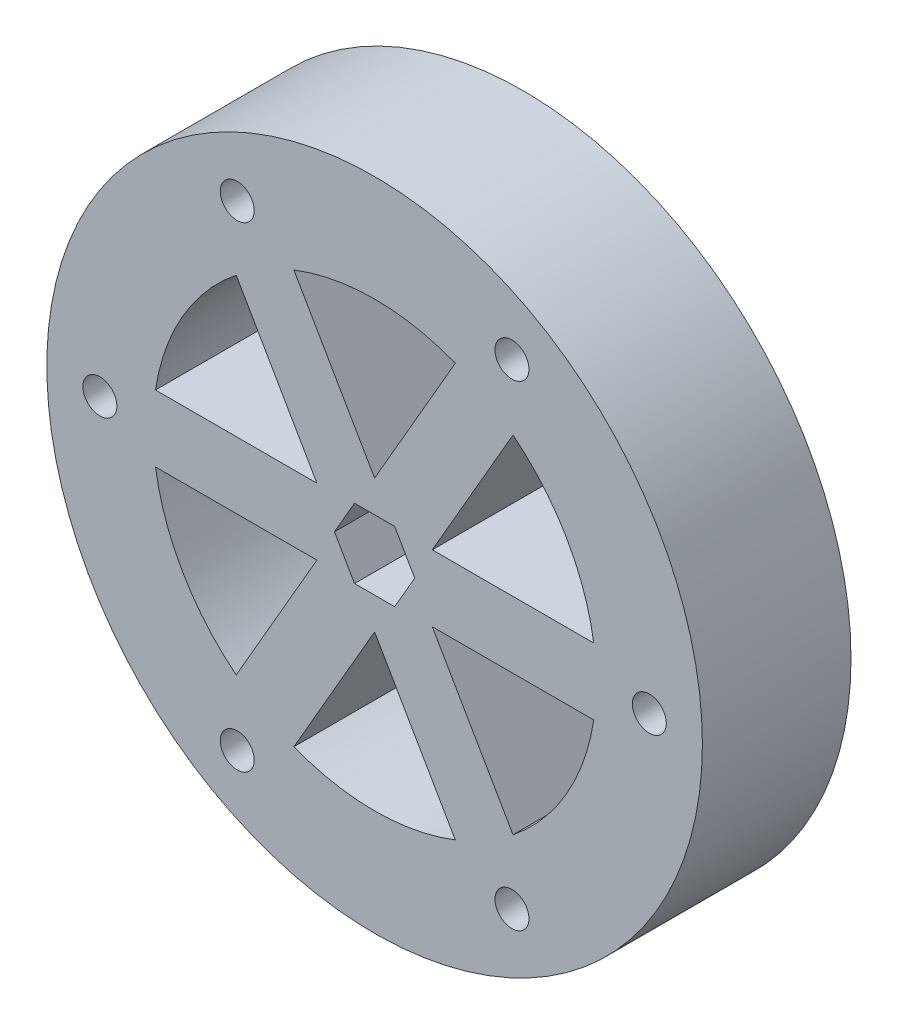
SolidWorks part; units mm, degrees
material "PET"
ref_plane "Front Plane" through (0, 0, 0) normal (0, 0, 1) x (1, 0, 0)
ref_plane "Top Plane" through (0, 0, 0) normal (0, 1, 0) x (1, 0, 0)
ref_plane "Right Plane" through (0, 0, 0) normal (1, 0, 0) x (0, 0, -1)
ref_axis "Axis1" through (0, 0, 18.2154) along (0, 0, -1)
sketch "Sketch1" plane through (0, 0, 0) normal (0, 0, 1) x (1, 0, 0)
  line L0 (-1.8908, 3.275) -> (-3.7816, 0) construction
  line L1 (-3.7816, 0) -> (-1.8908, -3.275) construction
  line L2 (-1.8908, -3.275) -> (1.8908, -3.275) construction
  line L3 (1.8908, -3.275) -> (3.7816, 0) construction
  line L4 (3.7816, 0) -> (1.8908, 3.275) construction
  line L5 (1.8908, 3.275) -> (-1.8908, 3.275) construction
  line L6 (-1.8908, 3.275) -> (-3.7816, 0)
  line L7 (-3.7816, 0) -> (-1.8908, -3.275)
  line L8 (-1.8908, -3.275) -> (1.8908, -3.275)
  line L9 (1.8908, -3.275) -> (3.7816, 0)
  line L10 (3.7816, 0) -> (1.8908, 3.275)
  line L11 (1.8908, 3.275) -> (-1.8908, 3.275)
  circle A0 centre (-12.9402, 22.4131) radius 1.6 construction
  circle A1 centre (-12.9402, 22.4131) radius 1.6
  circle A2 centre (12.9402, 22.4131) radius 1.6 construction
  circle A3 centre (12.9402, 22.4131) radius 1.6
  circle A4 centre (25.8804, 0) radius 1.6 construction
  circle A5 centre (25.8804, 0) radius 1.6
  circle A6 centre (12.9402, -22.4131) radius 1.6 construction
  circle A7 centre (12.9402, -22.4131) radius 1.6
  circle A8 centre (-12.9402, -22.4131) radius 1.6 construction
  circle A9 centre (-12.9402, -22.4131) radius 1.6
  circle A10 centre (-25.8804, 0) radius 1.6 construction
  circle A11 centre (-25.8804, 0) radius 1.6
  arc A12 (-1.6133, -37.4408) -> (-31.618, -20.1176) centre (-47.9402, -83.0349) ccw construction
  arc A13 (-1.6133, -37.4408) -> (-31.618, -20.1176) centre (-47.9402, -83.0349) ccw
sketch "Sketch2" plane through (0, 0, 0) normal (0, 0, 1) x (1, 0, 0)
  circle A0 centre (0, 0) radius 30.8804
  arc A1 (-1.6133, -37.4408) -> (-31.618, -20.1176) centre (-47.9402, -83.0349) ccw construction
extrude "Hub" add sketch "Sketch2" along normal blind 14
sketch "Sketch4" plane through (0, 0, 0) normal (0, 0, 1) x (1, 0, 0)
  line L0 (-1.8908, -3.275) -> (1.8908, -3.275) construction
  line L1 (-3.7816, 0) -> (-1.8908, -3.275) construction
  line L2 (-1.8908, 3.275) -> (-3.7816, 0) construction
  line L3 (1.8908, 3.275) -> (-1.8908, 3.275) construction
  line L4 (3.7816, 0) -> (1.8908, 3.275) construction
  line L5 (1.8908, -3.275) -> (3.7816, 0) construction
  line L6 (-1.8908, -3.275) -> (1.8908, -3.275)
  line L7 (-3.7816, 0) -> (-1.8908, -3.275)
  line L8 (-1.8908, 3.275) -> (-3.7816, 0)
  line L9 (1.8908, 3.275) -> (-1.8908, 3.275)
  line L10 (3.7816, 0) -> (1.8908, 3.275)
  line L11 (1.8908, -3.275) -> (3.7816, 0)
  circle A12 centre (12.9402, -22.4131) radius 1.6
  circle A13 centre (-12.9402, -22.4131) radius 1.6
  circle A14 centre (-25.8804, 0) radius 1.6
  circle A15 centre (-12.9402, 22.4131) radius 1.6
  circle A16 centre (12.9402, 22.4131) radius 1.6
  circle A17 centre (25.8804, 0) radius 1.6
  dimension "D1" = 3.2
extrude "Axle and screws" cut sketch "Sketch4" along normal through all
sketch "Sketch5" plane through (0, 0, 0) normal (0, 0, 1) x (1, 0, 0)
  line L0 (-5.4343, -3.1375) -> (-20.6433, -3.1375) construction
  line L1 (-13.0388, -16.3089) -> (-5.4343, -3.1375) construction
  line L2 (0, -6.275) -> (-7.6045, -19.4464) construction
  line L3 (7.6045, -19.4464) -> (0, -6.275) construction
  line L4 (5.4343, -3.1375) -> (13.0388, -16.3089) construction
  line L5 (20.6433, -3.1375) -> (5.4343, -3.1375) construction
  line L6 (5.4343, 3.1375) -> (20.6433, 3.1375) construction
  line L7 (13.0388, 16.3089) -> (5.4343, 3.1375) construction
  line L8 (-20.6433, 3.1375) -> (-5.4343, 3.1375) construction
  line L9 (-5.4343, 3.1375) -> (-13.0388, 16.3089) construction
  line L10 (0, 6.275) -> (7.6045, 19.4464) construction
  line L11 (-7.6045, 19.4464) -> (0, 6.275) construction
  line L12 (-5.4343, -3.1375) -> (-20.6433, -3.1375)
  line L13 (-13.0388, -16.3089) -> (-5.4343, -3.1375)
  line L14 (0, -6.275) -> (-7.6045, -19.4464)
  line L15 (7.6045, -19.4464) -> (0, -6.275)
  line L16 (5.4343, -3.1375) -> (13.0388, -16.3089)
  line L17 (20.6433, -3.1375) -> (5.4343, -3.1375)
  line L18 (5.4343, 3.1375) -> (20.6433, 3.1375)
  line L19 (13.0388, 16.3089) -> (5.4343, 3.1375)
  line L20 (-20.6433, 3.1375) -> (-5.4343, 3.1375)
  line L21 (-5.4343, 3.1375) -> (-13.0388, 16.3089)
  line L22 (0, 6.275) -> (7.6045, 19.4464)
  line L23 (-7.6045, 19.4464) -> (0, 6.275)
  arc A0 (-20.6433, -3.1375) -> (-13.0388, -16.3089) centre (0, 0) ccw construction
  arc A1 (-7.6045, -19.4464) -> (7.6045, -19.4464) centre (0, 0) ccw construction
  arc A2 (13.0388, -16.3089) -> (20.6433, -3.1375) centre (0, 0) ccw construction
  arc A3 (20.6433, 3.1375) -> (13.0388, 16.3089) centre (0, 0) ccw construction
  arc A4 (-13.0388, 16.3089) -> (-20.6433, 3.1375) centre (0, 0) ccw construction
  arc A5 (7.6045, 19.4464) -> (-7.6045, 19.4464) centre (0, 0) ccw construction
  arc A6 (-20.6433, -3.1375) -> (-13.0388, -16.3089) centre (0, 0) ccw
  arc A7 (-7.6045, -19.4464) -> (7.6045, -19.4464) centre (0, 0) ccw
  arc A8 (13.0388, -16.3089) -> (20.6433, -3.1375) centre (0, 0) ccw
  arc A9 (20.6433, 3.1375) -> (13.0388, 16.3089) centre (0, 0) ccw
  arc A10 (-13.0388, 16.3089) -> (-20.6433, 3.1375) centre (0, 0) ccw
  arc A11 (7.6045, 19.4464) -> (-7.6045, 19.4464) centre (0, 0) ccw
extrude "Ribs" cut sketch "Sketch5" along normal up to next
